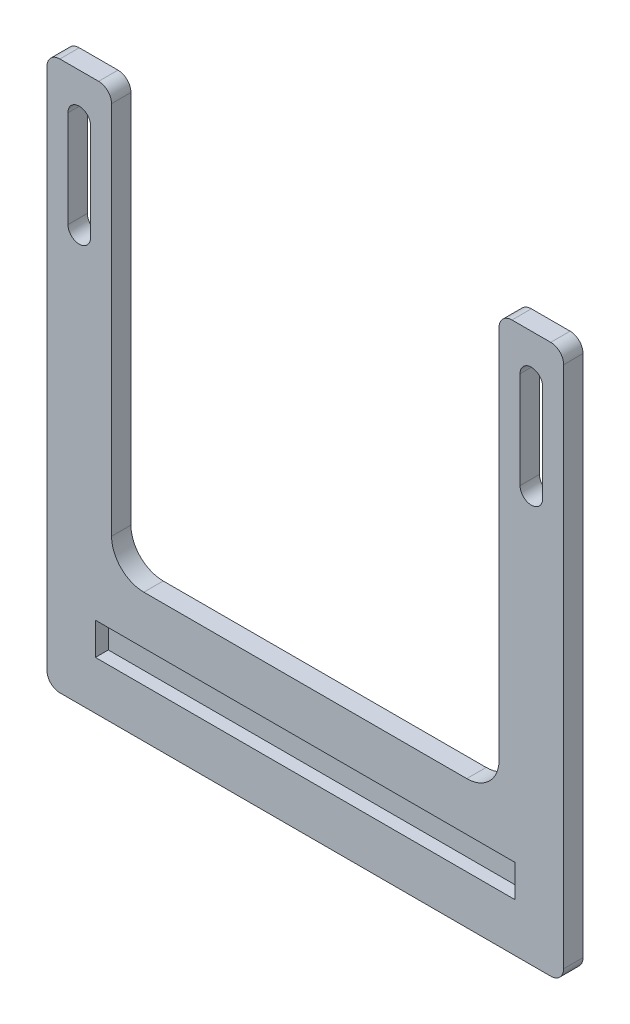
SolidWorks part; units mm, degrees
ref_plane "Alzado" through (0, 0, 0) normal (0, 0, 1) x (1, 0, 0)
ref_plane "Planta" through (0, 0, 0) normal (0, 1, 0) x (1, 0, 0)
ref_plane "Vista lateral" through (0, 0, 0) normal (1, 0, 0) x (0, 0, -1)
sketch "Croquis1" plane through (0, 0, 0) normal (0, 0, 1) x (1, 0, 0)
  line L0 (0, 94.9258) -> (0, -94.9258) construction
  line L1 (-30, 10) -> (30, 10)
  line L2 (-40, 10) -> (-40, -10)
  line L3 (-40, -10) -> (40, -10)
  line L4 (40, 10) -> (40, -10)
  line L5 (-40, 10) -> (40, -10) construction
  line L6 (-40, -10) -> (40, 10) construction
  line L8 (-40, 10) -> (-40, 75)
  line L9 (-40, 75) -> (-30, 75)
  line L10 (-30, 10) -> (-30, 75)
  line L11 (40, 75) -> (30, 75)
  line L12 (30, 10) -> (30, 75)
  line L14 (40, 10) -> (40, 75)
  line L15 (-35, 75) -> (-35, 47.1231) construction
  line L16 (35, 75) -> (35, 47.1231) construction
  line L17 (-35, 68.4155) -> (-35, 53.4155) construction
  line L18 (-33.25, 68.4155) -> (-33.25, 53.4155)
  line L19 (-36.75, 68.4155) -> (-36.75, 53.4155)
  line L20 (35, 68.4155) -> (35, 53.4155) construction
  line L21 (33.25, 68.4155) -> (33.25, 53.4155)
  line L22 (36.75, 68.4155) -> (36.75, 53.4155)
  line L24 (-32.5, 2.5) -> (32.5, 2.5)
  line L25 (-32.5, 2.5) -> (-32.5, -2.5)
  line L26 (-32.5, -2.5) -> (32.5, -2.5)
  line L27 (32.5, 2.5) -> (32.5, -2.5)
  line L28 (-32.5, 2.5) -> (32.5, -2.5) construction
  line L29 (-32.5, -2.5) -> (32.5, 2.5) construction
  arc A0 (-33.25, 68.4155) -> (-36.75, 68.4155) centre (-35, 68.4155) ccw
  arc A1 (-36.75, 53.4155) -> (-33.25, 53.4155) centre (-35, 53.4155) ccw
  arc A2 (33.25, 68.4155) -> (36.75, 68.4155) centre (35, 68.4155) cw
  arc A3 (36.75, 53.4155) -> (33.25, 53.4155) centre (35, 53.4155) cw
  point P0 (0, 0)
  point P12 (0, 0)
  point P21 (-35, 60.9155)
  point P28 (35, 60.9155)
  point P33 (0, 0)
  point P38 (0, 0)
  point P39 (-35, 22.0105)
  point P40 (-35, 47.1231)
  dimension "D6" = 1.75
  dimension "D1" = 20
  dimension "D2" = 80
  dimension "D3" = 65
  dimension "D4" = 10
  dimension "D5" = 15
  dimension "D7" = 5
  dimension "D8" = 65
extrude "Saliente-Extruir1" add sketch "Croquis1" along normal blind 3
extrude "Saliente-Extruir2" add sketch "Croquis1<3>" along normal blind 1 contours L27 L24 L25 L26 region at (0, 0, 0)
sketch "Croquis1<3>" plane through (0, 0, 0) normal (0, 0, 1) x (1, 0, 0) same geometry as "Croquis1"
fillet "Redondeo1" radius 5 2 edges at (30, 10, 1.5) (-30, 10, 1.5)
fillet "Redondeo2" radius 2 6 edges at (40, -10, 1.5) (-40, -10, 1.5) (40, 75, 1.5) (30, 75, 1.5) (-40, 75, 1.5) (-30, 75, 1.5)
